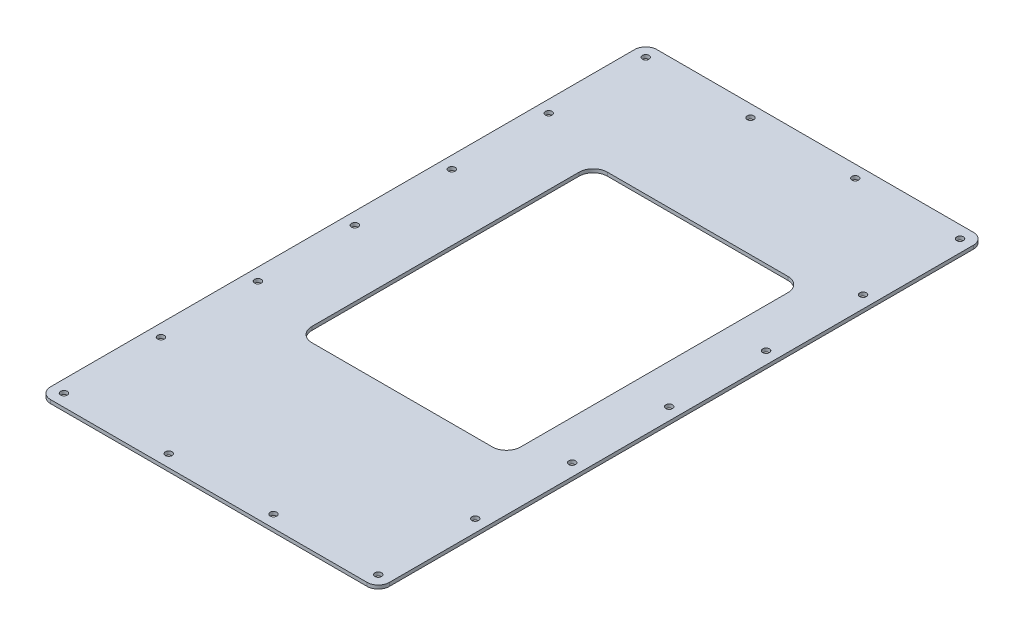
SolidWorks part; units mm, degrees
material "5052-H32"
ref_plane "Front Plane" through (0, 0, 0) normal (0, 0, 1) x (1, 0, 0)
ref_plane "Top Plane" through (0, 0, 0) normal (0, 1, 0) x (1, 0, 0)
ref_plane "Right Plane" through (0, 0, 0) normal (1, 0, 0) x (0, 0, -1)
sketch "Sketch9" plane through (0, 0, 0) normal (0, 1, 0) x (1, 0, 0)
  line L0 (-152, 0) -> (-152, 544)
  line L13 (-152, 544) -> (152, 544)
  line L14 (105.6625, 161.4438) -> (-81.6625, 161.4438)
  line L19 (152, 544) -> (152, 0)
  line L20 (105.6625, 161.4438) -> (105.6625, 426.5563)
  line L21 (105.6625, 426.5563) -> (-81.6625, 426.5563)
  line L22 (-81.6625, 161.4438) -> (-81.6625, 426.5563)
  line L23 (105.6625, 294) -> (-81.6625, 294) construction
  line L24 (12, 426.5562) -> (12, 161.4438) construction
  line L25 (-152, 0) -> (152, 0)
  point P8 (0, 0)
  point P19 (0, 0)
  dimension "D3" = 265.1125
  dimension "D4" = 187.325
  dimension "D1" = 304
  dimension "D2" = 544
  dimension "D6" = 140
  dimension "D5" = 250
extrude "Boss-Extrude7" add sketch "Sketch9" along normal blind 3.175 separate body contours L0 L25 L19 L13 L14 L22 L21 L20 region at (-145.7682, 0, -272)
fillet "Fillet4" radius 10 4 edges at (-152, 1.5875, -544) (152, 1.5875, -544) (-152, 1.5875, 0) (152, 1.5875, 0)
fillet "Fillet5" radius 12.7 4 edges at (-81.6625, 1.5875, -161.4438) (105.6625, 1.5875, -161.4438) (105.6625, 1.5875, -426.5563) (-81.6625, 1.5875, -426.5563)
sketch "Sketch10" plane through (0, 3.175, 0) normal (0, 1, 0) x (1, 0, 0)
  line L0 (-152, 10) -> (-152, 534) construction
  line L1 (-142, 0) -> (142, 0) construction
  circle A0 centre (-141, 11) radius 3
  circle A1 centre (-47, 11) radius 3
  circle A2 centre (47, 11) radius 3
  circle A3 centre (141, 11) radius 3
  circle A56 centre (-141, 98) radius 3
  circle A57 centre (-141, 185) radius 3
  circle A58 centre (-141, 272) radius 3
  circle A59 centre (-141, 359) radius 3
  circle A60 centre (-141, 446) radius 3
  circle A61 centre (-141, 533) radius 3
  circle A68 centre (141, 98) radius 3
  circle A72 centre (141, 185) radius 3
  circle A76 centre (141, 272) radius 3
  circle A80 centre (141, 359) radius 3
  circle A84 centre (141, 446) radius 3
  circle A86 centre (-47, 533) radius 3
  circle A87 centre (47, 533) radius 3
  circle A88 centre (141, 533) radius 3
  circle A102 centre (-47, 98) radius 3 [skipped]
  circle A103 centre (47, 98) radius 3 [skipped]
  circle A104 centre (-47, 185) radius 3 [skipped]
  circle A105 centre (47, 185) radius 3 [skipped]
  circle A106 centre (-47, 272) radius 3 [skipped]
  circle A107 centre (47, 272) radius 3 [skipped]
  circle A108 centre (-47, 359) radius 3 [skipped]
  circle A109 centre (47, 359) radius 3 [skipped]
  circle A110 centre (-47, 446) radius 3 [skipped]
  circle A111 centre (47, 446) radius 3 [skipped]
  dimension "D1" = 6
  dimension "D2" = 11
  dimension "D3" = 11
  dimension "D6" = 87
  dimension "D7" = 94
  dimension "D4" = 4
  dimension "D5" = 7
extrude "Cut-Extrude1" cut sketch "Sketch10" against normal up to surface (3.175 mm away) up to face at (12, 0, -294)
equation "\"W\"= 260"
equation "\"L\"= 500"
equation "\"Offset\"= 20"
equation "\"H\"= 110"
equation "\"Compartment Width\"= 90"
equation "\"T\"= 4.7625 * 2 / 3"
equation "\"Inside Fillet Radius\"= 5.55625"
equation "\"Hole\"=15"
equation "\"Wheel to Wall\"= 40"
equation "\"D1@Sketch9\"=\"W\"+44"
equation "\"D2@Sketch9\"=\"L\"+44"
equation "\"D6@Sketch10\"=(\"L\"+22)/6"
equation "\"D7@Sketch10\"=(\"W\"+22)/3"
equation "\"D5@Sketch9\"=(\"L\"/2+20)-\"Offset\""
